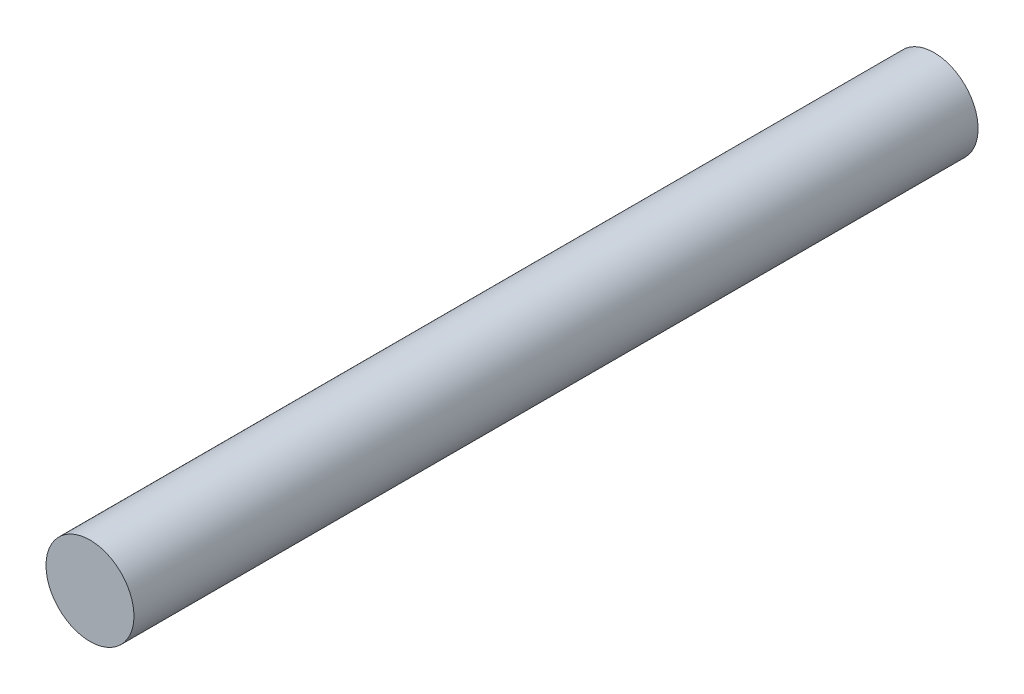
SolidWorks part; units mm, degrees
ref_plane "Front" through (0, 0, 0) normal (0, 0, 1) x (1, 0, 0)
ref_plane "Top" through (0, 0, 0) normal (0, 1, 0) x (1, 0, 0)
ref_plane "Right" through (0, 0, 0) normal (1, 0, 0) x (0, 0, -1)
sketch "Sketch1" plane through (0, 0, 0) normal (0, 0, 1) x (1, 0, 0)
  circle A0 centre (0, 0) radius 1.9844
  dimension "D1" = 3.9688
extrude "Boss-Extrude1" add sketch "Sketch1" along normal blind 38.1
